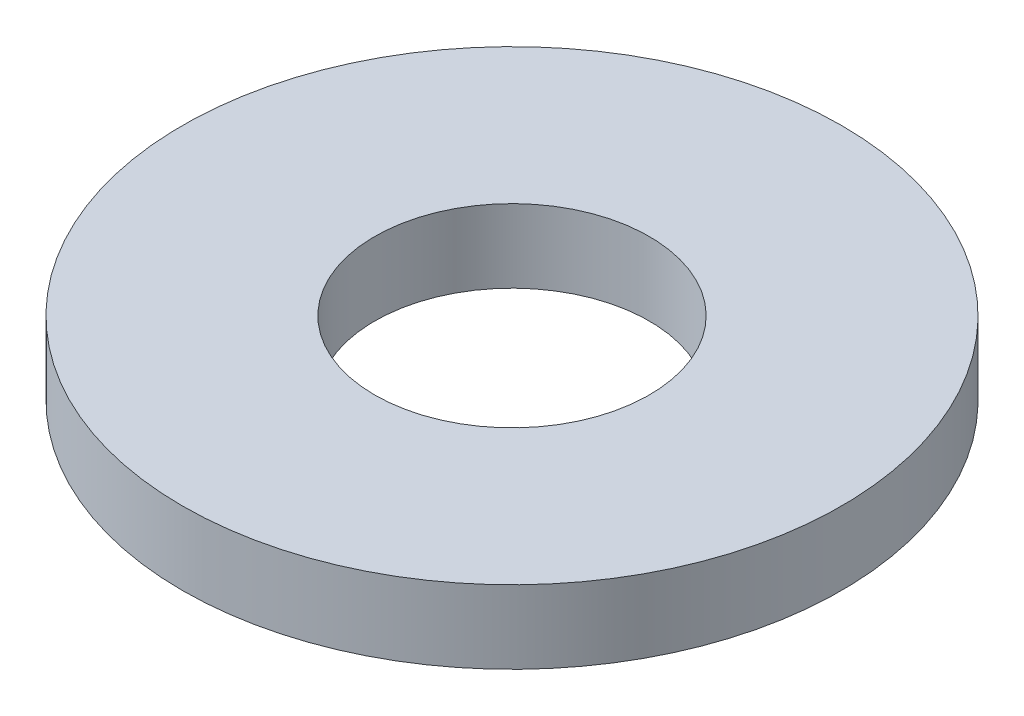
SolidWorks part; units mm, degrees
ref_plane "Front Plane" through (0, 0, 0) normal (0, 0, 1) x (1, 0, 0)
ref_plane "Top Plane" through (0, 0, 0) normal (0, 1, 0) x (1, 0, 0)
ref_plane "Right Plane" through (0, 0, 0) normal (1, 0, 0) x (0, 0, -1)
sketch "Sketch1" plane through (0, 0, 0) normal (0, 1, 0) x (1, 0, 0)
  circle A0 centre (0, 0) radius 90
  dimension "FLANGE_OD" = 180
extrude "Boss-Extrude1" add sketch "Sketch1" along normal blind 20
sketch "Sketch2" plane through (0, 0, 0) normal (0, 1, 0) x (1, 0, 0)
  circle A0 centre (0, 0) radius 37.5
  dimension "BORE_D" = 75
extrude "Cut-Extrude1" cut sketch "Sketch2" along normal through all
sketch "Sketch3" plane through (0, 20, 0) normal (0, 1, 0) x (1, 0, 0)
  circle A0 centre (0, 0) radius 30.7198 construction
  circle A1 centre (-30.7198, 0) radius 5.7365
  dimension "BOLT_D" = 11.4731
  dimension "BOLT_PCD" = 61.4395
extrude "Cut-Extrude2" cut sketch "Sketch3" against normal blind 16.9648 rebuild error yes
pattern_circular "CirPattern1" count 5 over 360 rebuild error yes
